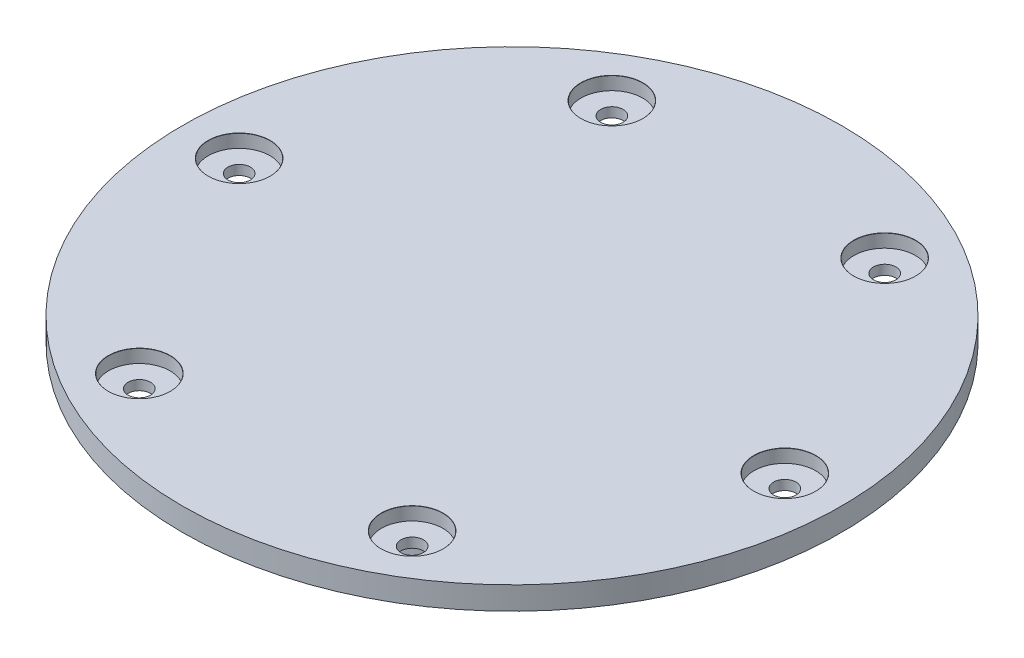
SolidWorks part; units mm, degrees
ref_plane "Plan de face" through (0, 0, 0) normal (0, 0, 1) x (1, 0, 0)
ref_plane "Plan de dessus" through (0, 0, 0) normal (0, 1, 0) x (1, 0, 0)
ref_plane "Plan de droite" through (0, 0, 0) normal (1, 0, 0) x (0, 0, -1)
sketch "Esquisse1" plane through (0, 0, 0) normal (0, 1, 0) x (1, 0, 0)
  circle A0 centre (0, 0) radius 32.53
  dimension "D1" = 65.06
extrude "Boss.-Extru.1" add sketch "Esquisse1" against normal blind 8.03
sketch "Esquisse2" plane through (0, 0, 0) normal (0, 1, 0) x (1, 0, 0)
  circle A0 centre (0, 0) radius 49.956
  dimension "D1" = 99.912
extrude "Boss.-Extru.2" add sketch "Esquisse2" along normal blind 3.47
sketch "Esquisse3" plane through (0, 3.47, 0) normal (0, 1, 0) x (1, 0, 0)
  line L0 (0, -41.356) -> (0, -49.956) construction
  line L1 (0, 0) -> (-20.678, -35.8153) construction
  line L2 (0, 0) -> (0, -41.356) construction
  line L3 (0, 0) -> (20.678, -35.8153) construction
  line L4 (-35.8153, 20.678) -> (-43.2632, 24.978) construction
  line L5 (0, 0) -> (-20.678, 35.8153) construction
  line L6 (0, 0) -> (-35.8153, 20.678) construction
  line L7 (0, 0) -> (-41.356, 0) construction
  line L8 (35.8153, 20.678) -> (43.2632, 24.978) construction
  line L9 (0, 0) -> (41.356, 0) construction
  line L10 (0, 0) -> (35.8153, 20.678) construction
  line L11 (0, 0) -> (20.678, 35.8153) construction
  circle A0 centre (0, 0) radius 41.356 construction
  circle A1 centre (0, 0) radius 49.956 construction
  circle A2 centre (0, -41.356) radius 1.25
  circle A3 centre (20.678, -35.8153) radius 1.25
  circle A5 centre (-20.678, -35.8153) radius 1.25
  circle A6 centre (-35.8153, 20.678) radius 1.25
  circle A7 centre (-41.356, 0) radius 1.25
  circle A8 centre (-20.678, 35.8153) radius 1.25
  circle A9 centre (35.8153, 20.678) radius 1.25
  circle A10 centre (20.678, 35.8153) radius 1.25
  circle A11 centre (41.356, 0) radius 1.25
  point P2 (0, -41.356)
  point P3 (0, -49.956)
  point P19 (-35.8153, 20.678)
  point P20 (-43.2632, 24.978)
  point P28 (35.8153, 20.678)
  point P29 (43.2632, 24.978)
  point P40 (0, 0)
  dimension "D1" = 8.6
  dimension "D5" = 3
  dimension "D2" = 2.5
  dimension "D4" = 30
  dimension "D6" = 82.712
  dimension "D3" = 30
sketch3d "Esquisse3D3"
  line L0 (0, 0, 0) -> (0, 67.4821, 0) construction
hole_wizard "Chambrage pour vis à tête hexagonale M33" positions "Esquisse3D4" profile "Esquisse6" counterbore size "M3" standard "Iso" end condition through all
sketch3d "Esquisse3D4"
  point P0 (-41.356, 3.47, 0)
  point P6 (-20.678, 3.47, -35.8153)
  point P9 (20.678, 3.47, -35.8153)
  point P15 (41.356, 3.47, 0)
  point P18 (20.678, 3.47, 35.8153)
  point P26 (-20.678, 3.47, 35.8153)
sketch "Esquisse6" plane through (-41.356, 3.47, 0) normal (1, 0, 0) x (0, 0, 1)
  line L0 (0, 0) -> (0, 11.5)
  line L1 (0, 11.5) -> (1.7, 11.5)
  line L3 (1.7, 11.5) -> (1.7, 2)
  line L4 (4.6755, 2) -> (1.7, 2)
  line L5 (4.6755, 2) -> (4.6755, 0.025)
  line L6 (4.6755, 0.025) -> (4.7005, 0)
  line L7 (4.7005, 0) -> (0, 0)
  line L8 (-4.6755, 0.025) -> (-4.7005, 0) construction
  line L11 (0, -6.35) -> (0, 107.95) construction
  dimension "Diamètre du perçage jusqu'au prochain" = 3.4
  dimension "Profondeur du perçage jusqu'au prochain" = 11.5
  dimension "Diamètre du chambrage" = 9.351
  dimension "Profondeur du chambrage" = 2
  dimension "Diamètre du fraisage entrant" = 9.401
  dimension "Angle du fraisage entrant" = 90
